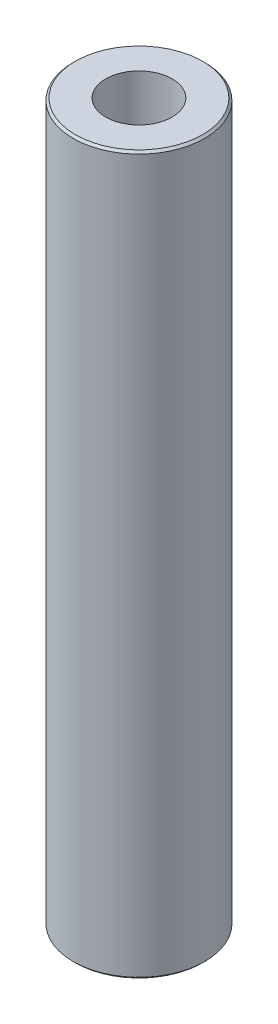
SolidWorks part; units mm, degrees
ref_plane "Front Plane" through (0, 0, 0) normal (0, 0, 1) x (1, 0, 0)
ref_plane "Top Plane" through (0, 0, 0) normal (0, 1, 0) x (1, 0, 0)
ref_plane "Right Plane" through (0, 0, 0) normal (1, 0, 0) x (0, 0, -1)
sketch "Sketch1" plane through (0, 0, 0) normal (0, 1, 0) x (1, 0, 0)
  circle A0 centre (0, 0) radius 42.5
  dimension "SHAFT_OD" = 85
extrude "Boss-Extrude1" add sketch "Sketch1" along normal blind 463.2898
sketch "Sketch2" plane through (0, 0, 0) normal (0, 1, 0) x (1, 0, 0)
  circle A0 centre (0, 0) radius 21.4344
  dimension "BORE_D" = 42.8688
extrude "Cut-Extrude1" cut sketch "Sketch2" along normal through all
chamfer "Chamfer1" distance 1.3983 angle 45 2 edges at (0, 463.2898, 42.5) (0, 0, 42.5)
